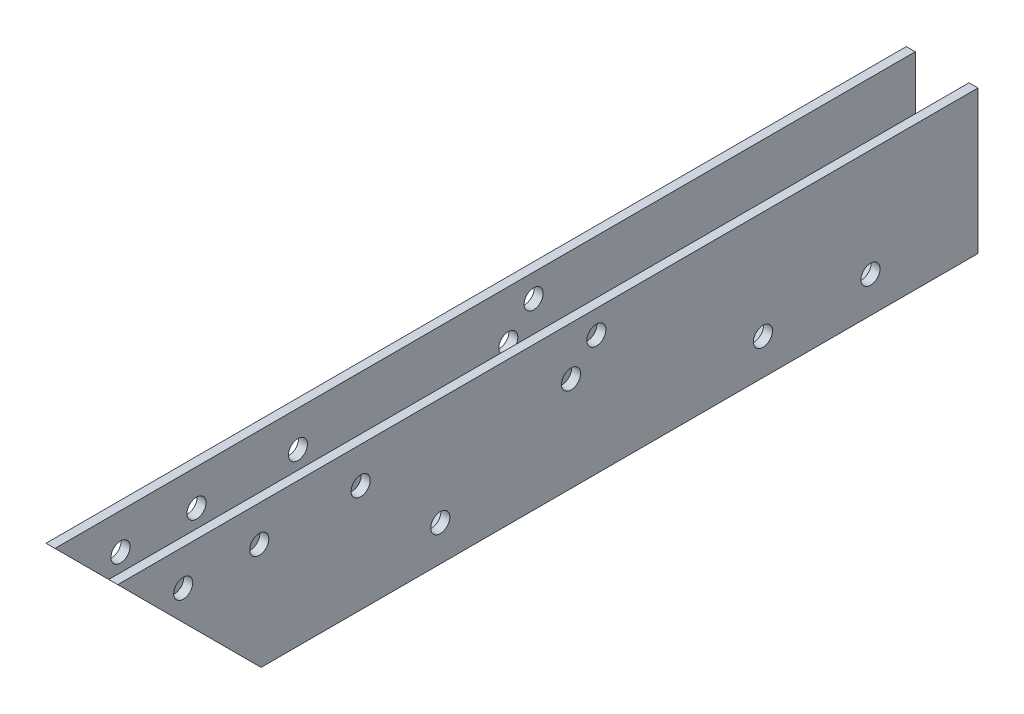
SolidWorks part; units mm, degrees
ref_plane "Front" through (0, 0, 0) normal (0, 0, 1) x (1, 0, 0)
ref_plane "Top" through (0, 0, 0) normal (0, 1, 0) x (1, 0, 0)
ref_plane "Right" through (0, 0, 0) normal (1, 0, 0) x (0, 0, -1)
sketch "Sketch1" plane through (0, 0, 0) normal (0, 0, 1) x (1, 0, 0)
  line L0 (0, -25.4) -> (0, 25.4) construction
  line L1 (-12.7, 0) -> (12.7, 0) construction
  line L2 (9.525, 25.4) -> (-9.525, 25.4) construction
  line L3 (-12.7, -25.4) -> (12.7, -25.4)
  line L4 (-12.7, -25.4) -> (-12.7, 25.4)
  line L5 (-12.7, 25.4) -> (12.7, 25.4)
  line L6 (12.7, -25.4) -> (12.7, 25.4)
  line L7 (-12.7, -25.4) -> (12.7, 25.4) construction
  line L8 (-12.7, 25.4) -> (12.7, -25.4) construction
  point P3 (0, 0)
  point P4 (0, 0)
  point P8 (0, 0)
  point P13 (12.7, 20.32)
  point P17 (0, 25.4)
  dimension "Outside Width" = 25.4
  dimension "Outside Height" = 50.8
  dimension "Inside Height" = 5.08
  dimension "Wall Thickness" = 3.175
sketch "Sketch2" plane through (0, 0, 0) normal (1, 0, 0) x (0, 0, -1)
  line L0 (-1219.2, 0) -> (1219.2, 0) construction
  dimension "Length" = 2438.4
sketch "Sketch3" plane through (0, 0, 0) normal (0, 0, 1) x (1, 0, 0)
  line L0 (-12.7, 25.4) -> (-12.7, -25.4)
  line L1 (-12.7, -25.4) -> (12.7, -25.4)
  line L2 (12.7, -25.4) -> (12.7, 25.4)
  line L3 (12.7, 25.4) -> (9.525, 25.4)
  line L4 (9.525, 25.4) -> (9.525, -22.225)
  line L5 (9.525, -22.225) -> (-9.525, -22.225)
  line L6 (-9.525, -22.225) -> (-9.525, 25.4)
  line L7 (-9.525, 25.4) -> (-12.7, 25.4)
  line L8 (-9.525, -22.225) -> (-9.525, -25.4) construction
  dimension "D2" = 25.4
  dimension "D3" = 3.175
extrude "Boss-Extrude2" add sketch "Sketch3" along normal mid plane 304.8
sketch "Reference Sketch1" plane through (0, 0, 0) normal (1, 0, 0) x (0, 0, -1)
  line L0 (-1219.2, 0) -> (1219.2, 0) construction
  point P0 (-1155.7, 0)
  point P1 (1155.7, 0)
  dimension "D1" = 63.5
sketch "Sketch4" plane through (12.7, 0, 0) normal (1, 0, 0) x (0, 0, -1)
  line L0 (-152.4, 25.4) -> (-101.6, -25.4)
  line L1 (-152.4, -25.4) -> (152.4, -25.4) construction
  line L2 (-101.6, -25.4) -> (-152.4, -25.4)
  line L3 (-152.4, -25.4) -> (-152.4, 25.4)
  dimension "D1" = 45
extrude "Cut-Extrude1" cut sketch "Sketch4" against normal through all
sketch "Sketch5" plane through (-12.7, 0, 0) normal (-1, 0, 0) x (0, 0, 1)
  circle A0 centre (-8.2099, 8.2099) radius 3.3782 construction
  circle A1 centre (-17.1901, 17.1901) radius 3.3782 construction
  circle A2 centre (-8.2099, 8.2099) radius 3.3782
  circle A3 centre (-17.1901, 17.1901) radius 3.3782
extrude "Cut-Extrude2" cut sketch "Sketch5" against normal through all
sketch "Sketch10" plane through (-12.7, 0, 0) normal (-1, 0, 0) x (0, 0, 1)
  circle A0 centre (66.3172, 12.7) radius 3.3782 construction
  circle A1 centre (66.3172, 12.7) radius 3.3782
  circle A2 centre (129.179, 12.7) radius 3.3782 construction
  circle A3 centre (102.2382, 12.7) radius 3.3782 construction
  circle A4 centre (129.179, 12.7) radius 3.3782
  circle A5 centre (102.2382, 12.7) radius 3.3782
extrude "Cut-Extrude3" cut sketch "Sketch10" against normal up to surface (25.4 mm away) up to face at (12.7, 4.8317, -8.2099)
hole_wizard "1/4 Clearance Hole1" positions "Sketch11" profile "Sketch12" hole size "1/4" standard "ANSI Inch"
sketch "Sketch11" plane through (-12.7, 0, 0) normal (-1, 0, 0) x (0, 0, 1)
  line L0 (-152.4, -12.7) -> (114.3, -12.7)
  line L1 (-152.4, 25.4) -> (-152.4, -25.4) construction
  line L2 (101.6, -25.4) -> (152.4, 25.4) construction
  line L4 (101.6, -25.4) -> (-152.4, -25.4) construction
  point P13 (-114.3, -12.7)
  point P15 (-76.2, -12.7)
  point P17 (38.1, -12.7)
  dimension "D1" = 12.7
  dimension "D2" = 38.1
  dimension "D3" = 38.1
  dimension "D4" = 114.3
sketch "Sketch12" plane through (-12.7, -12.7, 38.1) normal (0, 1, 0) x (0, 0, 1)
  line L0 (0, 0) -> (0, 27.4298)
  line L1 (0, 27.4298) -> (3.3782, 25.4)
  line L2 (3.3782, 25.4) -> (3.3782, 0)
  line L5 (3.3782, 0) -> (0, 0)
  line L10 (0, 27.4298) -> (-3.3782, 25.4) construction
  line L11 (0, -6.35) -> (0, 107.95) construction
  dimension "Hole Dia." = 6.7564
  dimension "Hole Depth" = 25.4
  dimension "Drill Angle" = 118
equation "\"D1@Sketch3\" = \"Outside Height@Sketch1\""
equation "\"D2@Sketch3\" = \"Outside Width@Sketch1\""
equation "\"D3@Sketch3\" = \"Wall Thickness@Sketch1\""
equation "\"D1@Reference Sketch1\" = \"Outside Height@Sketch1\" * 1.25"
equation "\"D2@Reference Sketch1\" = \"D1@Reference Sketch1\""
equation "\"D1@Boss-Extrude2\"=12in"
